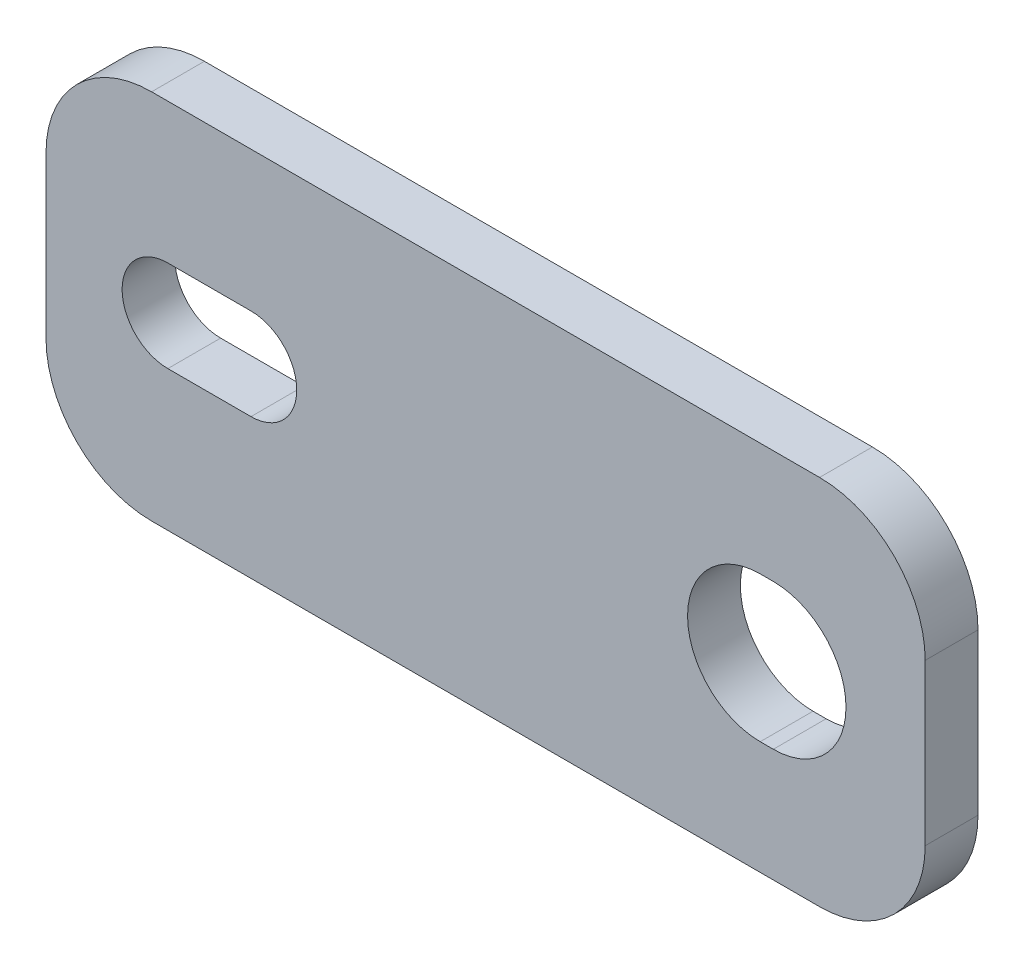
SolidWorks part; units mm, degrees
material "Custom Plastic"
ref_plane "X-Y Datum" through (0, 0, 0) normal (0, 0, 1) x (1, 0, 0)
ref_plane "X-Z Datum" through (0, 0, 0) normal (0, 1, 0) x (1, 0, 0)
ref_plane "Y-Z Datum" through (0, 0, 0) normal (1, 0, 0) x (0, 0, -1)
sketch "Sketch1" plane through (0, 0, 0) normal (0, 0, 1) x (1, 0, 0)
  line L0 (56.0374, 21.501) -> (56.0374, 0.851) construction
  line L1 (0, 0) -> (52.8624, 0)
  line L2 (0, 0) -> (0, 22.352)
  line L3 (0, 22.352) -> (52.8624, 22.352)
  line L4 (52.8624, 0) -> (52.8624, 22.352)
  dimension "D1" = 22.352
  dimension "D2" = 3.175
base flange "Base-Flange1" sketch "Sketch1" thickness 3.175 reverse thickness direction no parameters "D1"=1.5875
sketch "Sketch6" plane through (0, 0, 0) normal (0, 0, 1) x (1, 0, 0)
  line L0 (42.9437, 6.8072) -> (43.7311, 6.8072) construction
  line L1 (43.7311, 15.5448) -> (42.9437, 15.5448) construction
  line L2 (12.325, 8.426) -> (7.325, 8.426) construction
  line L3 (7.325, 13.926) -> (12.325, 13.926) construction
  line L4 (0, 22.352) -> (0, 0)
  line L5 (0, 0) -> (52.8624, 0)
  line L6 (52.8624, 0) -> (52.8624, 22.352)
  line L7 (52.8624, 22.352) -> (0, 22.352)
  line L8 (0, 22.352) -> (0, 0)
  line L9 (0, 0) -> (52.8624, 0)
  line L10 (52.8624, 0) -> (52.8624, 22.352)
  line L11 (52.8624, 22.352) -> (0, 22.352)
  line L12 (42.9437, 6.8072) -> (43.7311, 6.8072)
  line L13 (43.7311, 15.5448) -> (42.9437, 15.5448)
  line L14 (12.325, 8.426) -> (7.325, 8.426)
  line L15 (7.325, 13.926) -> (12.325, 13.926)
  arc A0 (42.9437, 15.5448) -> (42.9437, 6.8072) centre (42.9437, 11.176) ccw construction
  arc A1 (43.7311, 6.8072) -> (43.7311, 15.5448) centre (43.7311, 11.176) ccw construction
  arc A2 (12.325, 8.426) -> (12.325, 13.926) centre (12.325, 11.176) ccw construction
  arc A3 (7.325, 13.926) -> (7.325, 8.426) centre (7.325, 11.176) ccw construction
  arc A4 (42.9437, 15.5448) -> (42.9437, 6.8072) centre (42.9437, 11.176) ccw
  arc A5 (43.7311, 6.8072) -> (43.7311, 15.5448) centre (43.7311, 11.176) ccw
  arc A6 (12.325, 8.426) -> (12.325, 13.926) centre (12.325, 11.176) ccw
  arc A7 (7.325, 13.926) -> (7.325, 8.426) centre (7.325, 11.176) ccw
  dimension "D1" = 0
extrude "Cut-Extrude1" cut sketch "Sketch6" against normal blind 3.175 contours L15 A7 L14 A6 | L12 A5 L13 A4 normal cut yes
fillet "Fillet1" radius 6.35 4 edges at (52.8624, 22.352, -1.5875) (52.8624, 0, -1.5875) (0, 22.352, -1.5875) (0, 0, -1.5875)
sketch "Bend-Lines1" [suppressed] plane through (0, 0, 0) normal (0, 1, 0) x (1, 0, 0)
sketch "Bounding-Box1" [suppressed] plane through (0, 0, 0) normal (0, 1, 0) x (1, 0, 0)
sheet metal parameters "Sheet-Metal1" thickness 3.175 parameters "D1"=1.5875
flat pattern "Flat-Pattern1" [suppressed]
sketch "Bend-Lines2" plane through (0, 0, 0) normal (0, 1, 0) x (1, 0, 0)
sketch3d "Bounding-Box2" [suppressed]
  line L0 (0, 0, 0) -> (52.8624, 0, 0) construction
  line L1 (0, 22.352, 0) -> (52.8624, 22.352, 0) construction
  line L2 (0, 0, 0) -> (0, 22.352, 0) construction
  line L3 (52.8624, 0, 0) -> (52.8624, 22.352, 0) construction
sheet metal parameters "Sheet-Metal2" thickness 3.175 parameters "D1"=1.5875
flat pattern "Flat-Pattern1"
sketch "Bend-Lines2" plane through (0, 0, 0) normal (0, 1, 0) x (1, 0, 0)
sketch3d "Bounding-Box2" [suppressed]
  line L0 (0, 22.352, 0) -> (52.8624, 22.352, 0) construction
  line L1 (0, 0, 0) -> (52.8624, 0, 0) construction
  line L2 (0, 22.352, 0) -> (0, 0, 0) construction
  line L3 (52.8624, 22.352, 0) -> (52.8624, 0, 0) construction
